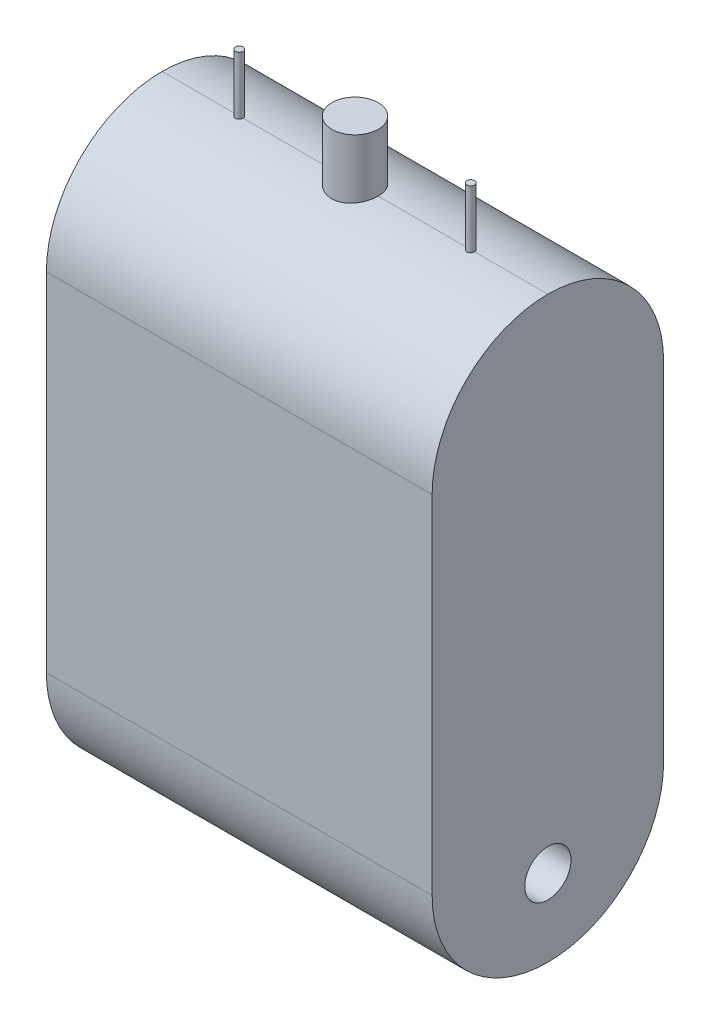
SolidWorks part; units mm, degrees
ref_plane "前视基准面" through (0, 0, 0) normal (0, 0, 1) x (1, 0, 0)
ref_plane "上视基准面" through (0, 0, 0) normal (0, 1, 0) x (1, 0, 0)
ref_plane "右视基准面" through (0, 0, 0) normal (1, 0, 0) x (0, 0, -1)
sketch "草图1" plane through (0, 0, 0) normal (0, 0, 1) x (1, 0, 0)
  line L0 (0, 0) -> (25, 0) construction
  line L1 (25, 0) -> (25, 42.5)
  line L2 (25, 42.5) -> (-25, 42.5)
  line L3 (-25, 42.5) -> (-25, -32.5)
  line L4 (-25, -32.5) -> (25, -32.5)
  line L5 (25, -32.5) -> (25, 0)
  dimension "D1" = 25
  dimension "D2" = 42.5
  dimension "D3" = 50
  dimension "D4" = 75
extrude "凸台-拉伸1" add sketch "草图1" along normal blind 30
sketch "草图2" plane through (25, 0, 0) normal (1, 0, 0) x (0, 0, -1)
  line L0 (0, -32.5) -> (0, -22.5) construction
  line L1 (0, -32.5) -> (0, 42.5) construction
  line L2 (0, -22.5) -> (-15, -22.5) construction
  circle A0 centre (-15, -22.5) radius 3
  dimension "D3" = 6
  dimension "D1" = 10
  dimension "D2" = 15
extrude "切除-拉伸1" cut sketch "草图2" against normal blind 52
fillet "圆角1" radius 15 1 edges at (0, -32.5, 0)
fillet "圆角2" radius 15 3 edges at (0, -32.5, 30) (25, -32.5, 22.5) (-25, -32.5, 22.5)
fillet "圆角3" radius 15 1 edges at (0, 42.5, 30)
fillet "圆角4" radius 15 3 edges at (-25, 42.5, 7.5) (25, 42.5, 7.5) (0, 42.5, 0)
sketch "草图4" plane through (0, 0, 0) normal (0, 1, 0) x (1, 0, 0)
  line L0 (-25, -15) -> (25, -15) construction
  line L1 (0, -15) -> (-15, -15) construction
  line L2 (0, -15) -> (15, -15) construction
  circle A0 centre (0, -15) radius 3
  circle A2 centre (15, -15) radius 0.5
  circle A3 centre (-15, -15) radius 0.5
  dimension "D1" = 6
  dimension "D2" = 15
  dimension "D3" = 1
  dimension "D5" = 1
  dimension "D4" = 15
extrude "凸台-拉伸2" add sketch "草图4" along normal blind 50
